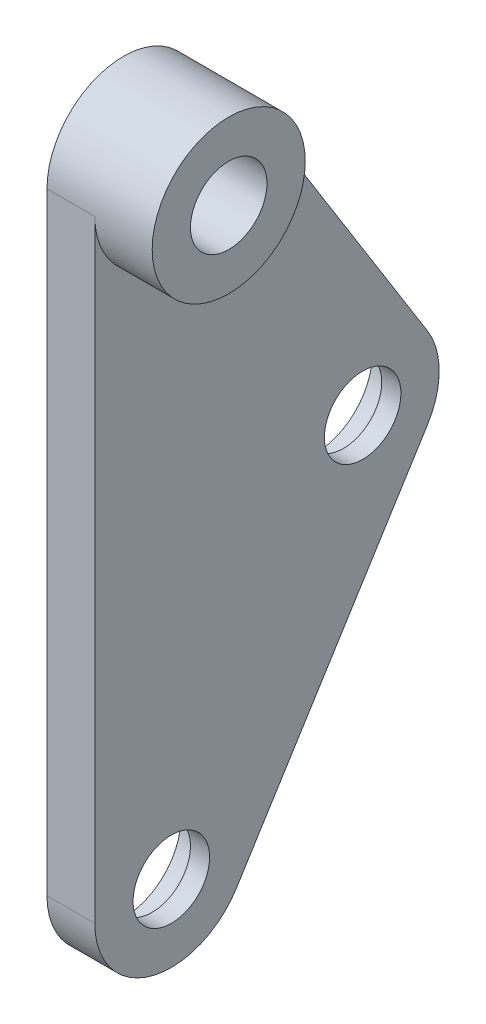
SolidWorks part; units mm, degrees
ref_plane "前视基准面" through (0, 0, 0) normal (0, 0, 1) x (1, 0, 0)
ref_plane "上视基准面" through (0, 0, 0) normal (0, 1, 0) x (1, 0, 0)
ref_plane "右视基准面" through (0, 0, 0) normal (1, 0, 0) x (0, 0, -1)
other "Configuration Table"
sketch "草图1" plane through (0, 0, 0) normal (1, 0, 0) x (0, 0, -1)
  line L0 (0, -20) -> (18, -20) construction
  line L1 (0, 0) -> (18, 0) construction
  line L2 (0, 0) -> (0, -40)
  line L3 (0, -40) -> (18, -40) construction
  line L4 (18, 0) -> (18, -40) construction
  line L5 (7.392, -1.88) -> (17.392, -17.88)
  line L6 (17.392, -22.12) -> (7.392, -38.12)
  circle A0 centre (4, -4) radius 4
  circle A1 centre (4, -36) radius 4
  circle A2 centre (14, -20) radius 4
  circle A3 centre (4, -4) radius 2
  circle A4 centre (14, -20) radius 2
  circle A5 centre (4, -36) radius 2
  dimension "D1" = 8
  dimension "D2" = 4
  dimension "D3" = 40
  dimension "D4" = 18
extrude "凸台-拉伸1" add sketch "草图1" along normal blind 2.5 contours A2 L5 A0 L2 A1 L6 | A0 | A2 | A1 region at (0, -20, -6.5849)
extrude "凸台-拉伸2" add sketch "草图1<4>" along normal blind 3 from surface contours A0 starting at face at (2.5, -20, -8.0964)
sketch "草图1<4>" plane through (0, 0, 0) normal (1, 0, 0) x (0, 0, -1) same geometry as "草图1"
extrude "切除-拉伸1" cut sketch "草图1<3>" along normal through all both and the other way through all contours A3 | A4 | A5
sketch "草图1<3>" plane through (0, 0, 0) normal (1, 0, 0) x (0, 0, -1) same geometry as "草图1"
sketch "草图2" plane through (0, 0, 0) normal (-1, 0, 0) x (0, 0, 1)
  circle A0 centre (-4, -4) radius 3
  circle A1 centre (-14, -20) radius 3
  circle A2 centre (-4, -36) radius 3
  dimension "D1" = 6
extrude "切除-拉伸2" cut sketch "草图2" against normal blind 1.5
